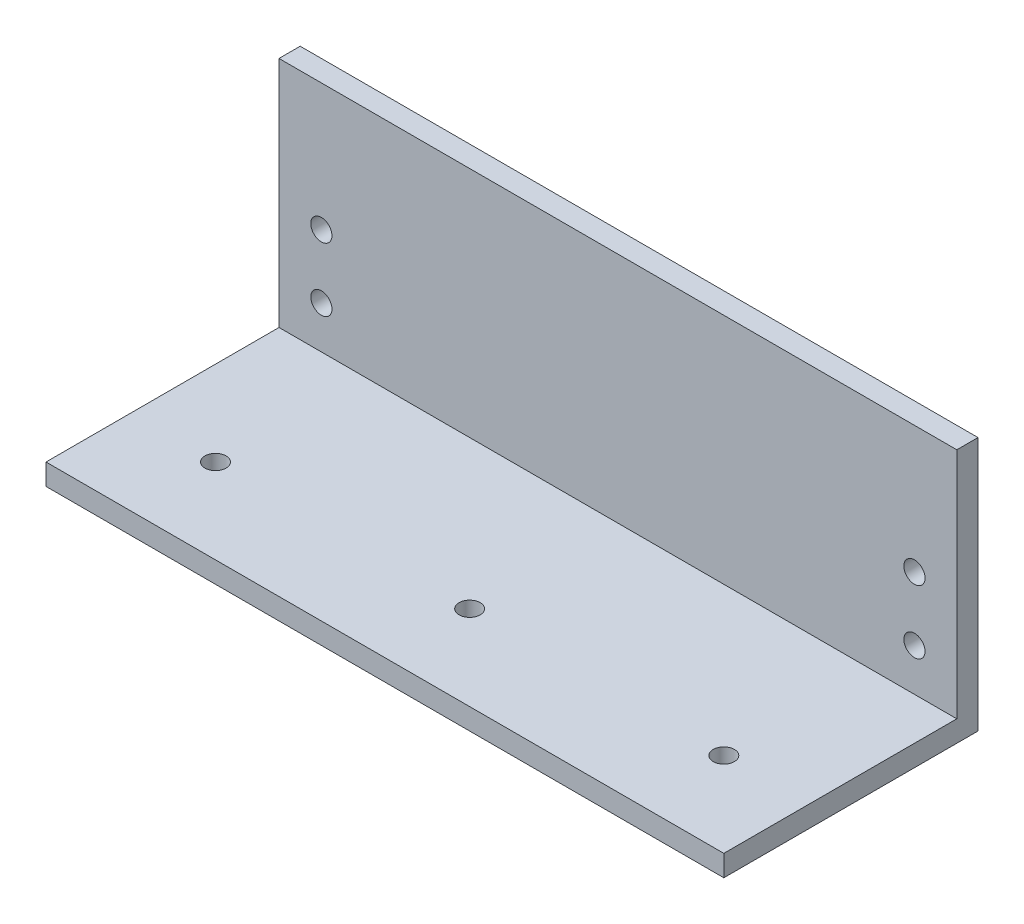
SolidWorks part; units mm, degrees
ref_plane "Front Plane" through (0, 0, 0) normal (0, 0, 1) x (1, 0, 0)
ref_plane "Top Plane" through (0, 0, 0) normal (0, 1, 0) x (1, 0, 0)
ref_plane "Right Plane" through (0, 0, 0) normal (1, 0, 0) x (0, 0, -1)
sketch "Sketch2" plane through (0, 0, 0) normal (1, 0, 0) x (0, 0, -1)
  line L1 (0, 0) -> (76.2, 0)
  line L2 (0, 0) -> (0, 76.2)
  line L3 (0, 76.2) -> (76.2, 76.2)
  line L4 (76.2, 0) -> (76.2, 76.2)
  line L5 (0, 76.2) -> (69.85, 76.2)
  line L6 (0, 76.2) -> (0, 6.35)
  line L7 (0, 6.35) -> (69.85, 6.35)
  line L8 (69.85, 76.2) -> (69.85, 6.35)
  dimension "D1" = 76.2
  dimension "D2" = 76.2
  dimension "D3" = 6.35
  dimension "D4" = 6.35
extrude "Boss-Extrude2" add sketch "Sketch2" along normal blind 203.2 contours L3 L8 L7 L2 L1 L4 region at (0, 3.175, -1.0776)
sketch "Sketch4" plane through (0, 0, -76.2) normal (0, 0, -1) x (-1, 0, 0)
  line L0 (-203.2, 0) -> (0, 0) construction
  line L1 (-203.2, 0) -> (-203.2, 76.2) construction
  circle A0 centre (-190.5, 19.05) radius 3.175
  circle A1 centre (-190.5, 38.1) radius 3.175
  circle A2 centre (-12.7, 19.05) radius 3.175
  circle A3 centre (-12.7, 38.1) radius 3.175
  dimension "D1" = 19.05
  dimension "D2" = 12.7
  dimension "D3" = 38.1
  dimension "D4" = 190.5
  dimension "D5" = 38.1
  dimension "D6" = 190.5
extrude "Cut-Extrude1" cut sketch "Sketch4" against normal blind 71.628
sketch "Sketch5" plane through (0, 6.35, 0) normal (0, 1, 0) x (1, 0, 0)
  line L0 (0, 0) -> (0, 69.85) construction
  line L1 (203.2, 0) -> (0, 0) construction
  circle A0 centre (25.4, 25.4) radius 3.175
  circle A1 centre (177.8, 25.4) radius 3.175
  circle A2 centre (101.6, 25.4) radius 3.175
  dimension "D1" = 177.8
  dimension "D2" = 6.35
  dimension "D3" = 25.4
  dimension "D4" = 101.6
  dimension "D5" = 25.4
  dimension "D6" = 25.4
  dimension "D7" = 25.4
extrude "Cut-Extrude2" cut sketch "Sketch5" against normal blind 244.602
